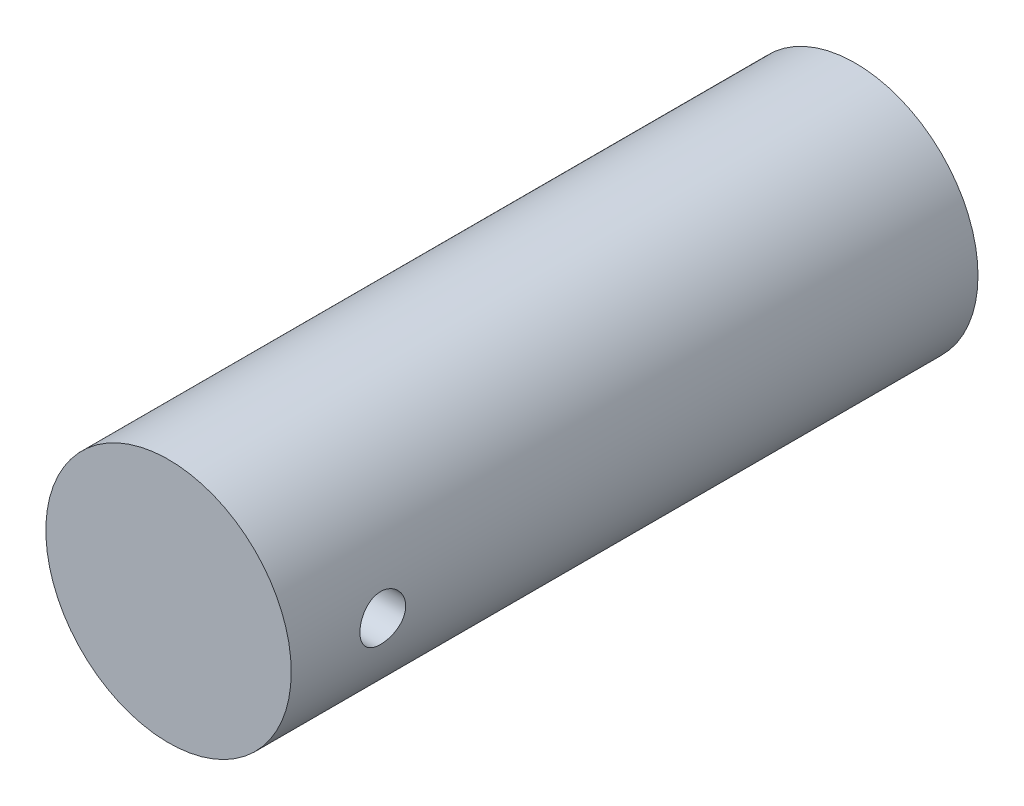
SolidWorks part; units mm, degrees
material "6061-T6 (SS)"
ref_plane "Front Plane" through (0, 0, 0) normal (0, 0, 1) x (1, 0, 0)
ref_plane "Top Plane" through (0, 0, 0) normal (0, 1, 0) x (1, 0, 0)
ref_plane "Right Plane" through (0, 0, 0) normal (1, 0, 0) x (0, 0, -1)
sketch "Sketch1" plane through (0, 0, 0) normal (0, 0, 1) x (1, 0, 0)
  circle A0 centre (0, 0) radius 8.509
  dimension "D1" = 17.018
extrude "Boss-Extrude1" add sketch "Sketch1" along normal blind 47.625
sketch "Sketch2" plane through (0, 0, 0) normal (1, 0, 0) x (0, 0, -1)
  line L0 (-47.625, 0) -> (0, 0) construction
  line L1 (-47.625, 8.509) -> (-47.625, -8.509) construction
  circle A0 centre (-41.275, 0) radius 1.5875
  point P7 (0, 0)
  dimension "D1" = 3.175
  dimension "D2" = 6.35
extrude "Cut-Extrude1" cut sketch "Sketch2" against normal blind 47.625 and the other way blind 47.625
